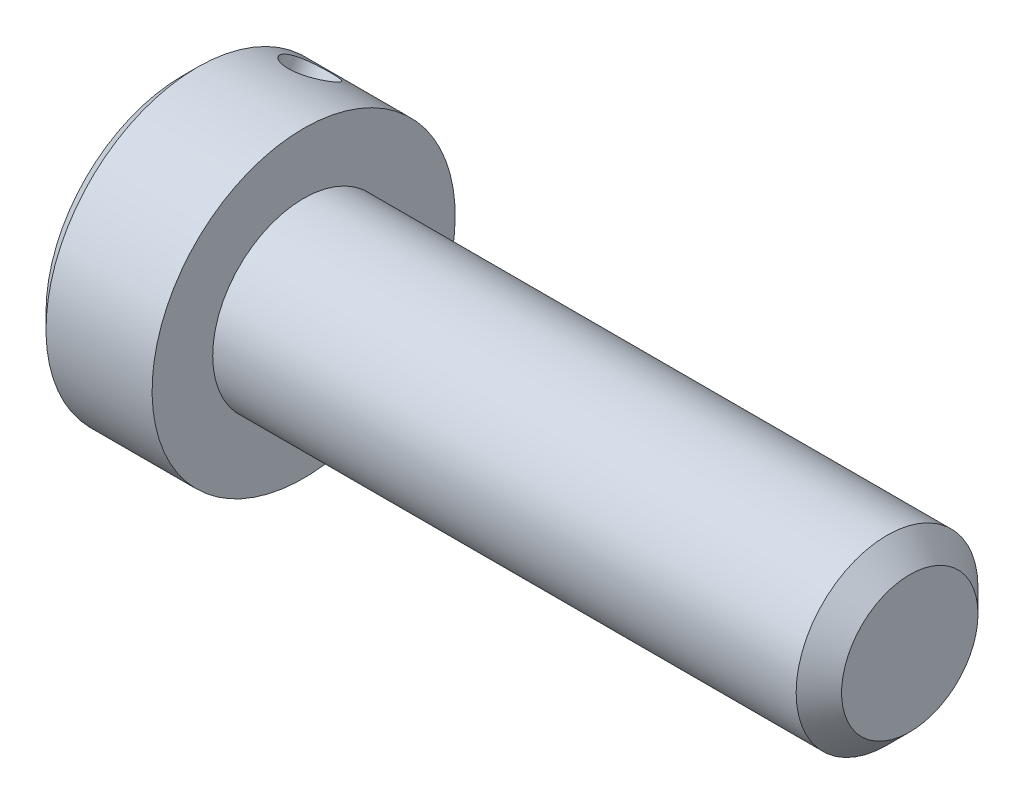
SolidWorks part; units mm, degrees
material "Alloy Steel"
ref_plane "Front Plane" through (0, 0, 0) normal (0, 0, 1) x (1, 0, 0)
ref_plane "Top Plane" through (0, 0, 0) normal (0, 1, 0) x (1, 0, 0)
ref_plane "Right Plane" through (0, 0, 0) normal (1, 0, 0) x (0, 0, -1)
sketch "Sketch1" plane through (0, 0, 0) normal (0, 0, 1) x (1, 0, 0)
  line L0 (10, 0) -> (-10, 0) construction
  line L1 (10, 3) -> (10, -3) construction
  line L2 (-10, 5) -> (-10, -5) construction
  line L3 (-10, 5) -> (-13.5, 5) construction
  line L4 (-13.5, 5) -> (-14, 4.5) construction
  line L5 (-14, 4.5) -> (-14, -4.5) construction
  line L6 (-14, -4.5) -> (-13.5, -5) construction
  line L7 (-13.5, -5) -> (-10, -5) construction
  point P7 (-10.88, 0)
  point P12 (6, -3)
  dimension "D1" = 45
  dimension "Dec." = 6
  dimension "Length" = 20
  dimension "Head Dia" = 10
  dimension "Head Height" = 4
  dimension "Hex Depth" = 3.12
  dimension "Chamfer" = 0.5
  dimension "D2" = 4
ref_plane "Plane1" through (10, 0, 0) normal (1, 0, 0) x (0, 0, -1)
ref_plane "Plane2" through (-14, 0, 0) normal (1, 0, 0) x (0, 0, -1)
sketch "Sketch2" plane through (10, 0, 0) normal (1, 0, 0) x (0, 0, -1)
  circle A0 centre (0, 0) radius 3
extrude "Boss-Extrude1" add sketch "Sketch2" against normal up to vertex (20 mm away) up to point (-10, 0, 0)
sketch "Sketch3" plane through (10, 0, 0) normal (1, 0, 0) x (0, 0, -1)
  circle A0 centre (0, 0) radius 3 construction
  circle A1 centre (0, 0) radius 3
curve "Helix/Spiral1" pitch 1 height 21 turns 21 parameters "Pitch"=1
chamfer "Chamfer1" distance 0.75 angle 45 1 edges at (10, 0, -3)
sketch "Sketch5" plane through (0, 0, 0) normal (0, 0, 1) x (1, 0, 0)
  line L0 (9.5625, 3) -> (10.4375, 3)
  line L1 (10.4375, 3) -> (10.0625, 2.3505)
  line L2 (10.0625, 2.3505) -> (9.9375, 2.3505)
  line L3 (9.9375, 2.3505) -> (9.5625, 3)
  line L4 (10, 2.3505) -> (10, 3) construction
  line L5 (9.75, 2.6752) -> (10.25, 2.6752) construction
  dimension "D1" = 60
  dimension "D2" = 0.5
  dimension "D3" = 0.125
sweep "Cut-Sweep1" [suppressed] cut profiles "Sketch5" path "Helix/Spiral1"
sketch "Sketch4" plane through (-14, 0, 0) normal (1, 0, 0) x (0, 0, -1)
  line L0 (-5, 0.7937) -> (5, 0.7937) construction
  line L1 (0, 2.3094) -> (-2, 1.1547)
  line L2 (-2, 1.1547) -> (-2, -1.1547)
  line L3 (-2, -1.1547) -> (0, -2.3094)
  line L4 (0, -2.3094) -> (2, -1.1547)
  line L5 (2, -1.1547) -> (2, 1.1547)
  line L6 (2, 1.1547) -> (0, 2.3094)
  line L7 (0, 0) -> (0, 0.7937) construction
  circle A0 centre (0, 0) radius 2 construction
  dimension "Hex Size" = 4
  dimension "D1" = 10
  dimension "D2" = 0.7937
sketch "Sketch6" plane through (0, 0, 0) normal (0, 0, 1) x (1, 0, 0)
  line L0 (-13.5, 5) -> (-14, 4.5) construction
  line L1 (-10, 5) -> (-13.5, 5) construction
  line L2 (-10, 5) -> (-10, -5) construction
  line L3 (-14, 4.5) -> (-14, -4.5) construction
  line L4 (-13.5, 5) -> (-14, 4.5)
  line L5 (-10, 5) -> (-13.5, 5)
  line L6 (-10, 5) -> (-10, 0)
  line L7 (-14, 4.5) -> (-14, 0)
  line L8 (-10, 0) -> (-14, 0) construction
  line L9 (-10, 0) -> (-14, 0)
revolve "Revolve1" add sketch "Sketch6" angle 360 about L8
extrude "Cut-Extrude1" cut sketch "Sketch4" along normal up to vertex (3.12 mm away) up to point (-10.88, 0, 0)
sketch "Sketch8" plane through (-14, 0, 0) normal (-1, 0, 0) x (0, 0, 1)
  circle A1 centre (0, 0) radius 2.3094
extrude "Cut-Extrude2" cut sketch "Sketch8" against normal through all draft 45
sketch "Sketch9" plane through (0, -1.7321, 1) normal (0, 0.866, -0.5) x (1, 0, 0)
  line L0 (-13.6906, 0) -> (-10.88, 0) construction
  line L1 (-10.88, -1.1547) -> (-10.88, 1.1547) construction
  circle A0 centre (-12.2853, 0) radius 0.7937
  spline S0 degree 3 poles (-14, -1.1547) (-13.9098, -0.9743) (-13.8331, -0.7898) (-13.7509, -0.5031) (-13.729, -0.4059) (-13.6989, -0.2073) (-13.6908, -0.1051) (-13.6902, 0.1974) (-13.7207, 0.3955) (-13.8314, 0.7863) (-13.9092, 0.9732) (-14, 1.1547) knots 0 0 0 0 0.25 0.25 0.375 0.375 0.5 0.5 0.75 0.75 1 1 1 1 construction
  dimension "D1" = 1.5875
extrude "Cut-Extrude3" cut sketch "Sketch9" against normal through all both and the other way through all contours A0
equation "\"D3@Helix/Spiral1\" = \"Length@Sketch1\"+\"Pitch@Helix/Spiral1\""
equation "\"D3@Sketch5\" = \"Pitch@Helix/Spiral1\"*.125"
equation "\"D2@Sketch5\" = \"Pitch@Helix/Spiral1\"*.50"
equation "\"D1@Chamfer1\" = \"Pitch@Helix/Spiral1\"*.75"
equation "\"D2@Sketch1\" = \"Pitch@Helix/Spiral1\"*4"
equation "\"D1@Sketch4\" = \"Head Dia@Sketch1\""
equation "\"Chamfer@Sketch1\" = \"Head Height@Sketch1\"/8"
